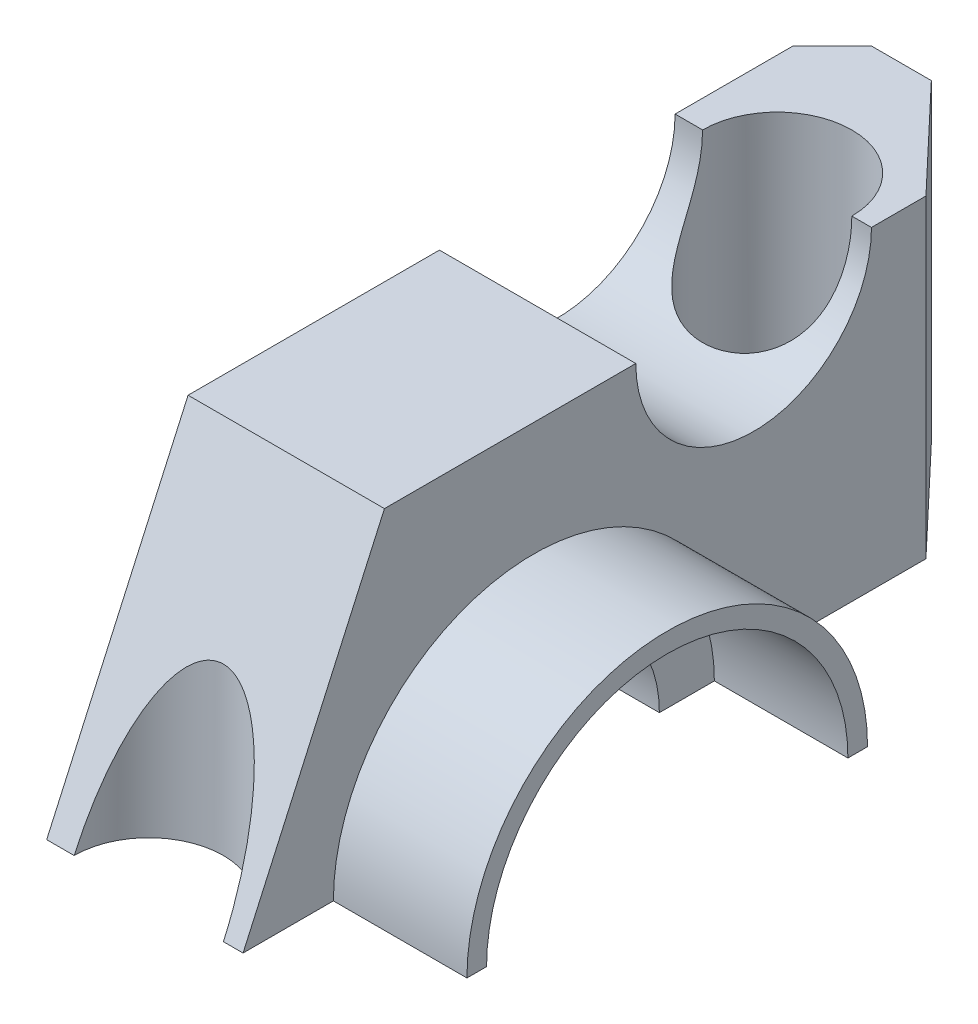
SolidWorks part; units mm, degrees
ref_plane "Alzado" through (0, 0, 0) normal (0, 0, 1) x (1, 0, 0)
ref_plane "Planta" through (0, 0, 0) normal (0, 1, 0) x (1, 0, 0)
ref_plane "Vista lateral" through (0, 0, 0) normal (1, 0, 0) x (0, 0, -1)
sketch "Croquis1" plane through (0, 0, 0) normal (1, 0, 0) x (0, 0, -1)
  line L0 (-100, 0) -> (-82, 40)
  line L1 (0, 0) -> (-100, 0)
  line L2 (0, 0) -> (0, 40)
  line L3 (0, 40) -> (-82, 40)
  dimension "D1" = 40
  dimension "D2" = 100
  dimension "D3" = 82
extrude "Saliente-Extruir1" add sketch "Croquis1" along normal blind 25
sketch "Croquis2" plane through (0, 40, 0) normal (0, 1, 0) x (1, 0, 0)
  line L1 (25, 0) -> (0, 0) construction
  line L2 (0, 0) -> (0, -82) construction
  circle A0 centre (13, -100) radius 9.5
  circle A1 centre (13, -20) radius 9.5
  point P8 (0, 0)
  dimension "D1" = 19
  dimension "D2" = 19
  dimension "D3" = 20
  dimension "D4" = 13
  dimension "D5" = 13
extrude "Cortar-Extruir1" cut sketch "Croquis2" against normal blind 94 and the other way blind 54
sketch "Croquis3" plane through (25, 0, 0) normal (1, 0, 0) x (0, 0, -1)
  line L0 (0, 40) -> (-82, 40) construction
  line L1 (0, 0) -> (0, 40) construction
  line L2 (-100, 0) -> (0, 0) construction
  circle A0 centre (-35, 40) radius 15
  circle A1 centre (-63, 0) radius 16
  dimension "D1" = 30
  dimension "D3" = 32
  dimension "D2" = 35
  dimension "D4" = 63
extrude "Cortar-Extruir2" cut sketch "Croquis3" against normal blind 94 and the other way blind 94
sketch "Croquis4" plane through (0, 40, 0) normal (0, 1, 0) x (1, 0, 0)
  line L0 (12.62, 0) -> (25, -13.0666)
  line L1 (25, 0) -> (0, 0) construction
  line L2 (25, 0) -> (25, -20) construction
  line L3 (0, 0) -> (0, -20) construction
  line L4 (12.62, 0) -> (25, 0)
  line L5 (25, 0) -> (25, -13.0666)
  dimension "D1" = 18
  dimension "D2" = 12.62
extrude "Cortar-Extruir3" cut sketch "Croquis4" against normal blind 94 and the other way blind 94
chamfer "Chaflán2" distance 5 angle 45 1 edges at (0, 20, 0)
sketch "Croquis5" plane through (25, 0, 0) normal (1, 0, 0) x (0, 0, -1)
  line L0 (-88.5, 0) -> (-86, 0)
  line L1 (-40, 0) -> (-37.5, 0)
  arc A0 (-40, 0) -> (-86, 0) centre (-63, 0) ccw
  arc A1 (-37.5, 0) -> (-88.5, 0) centre (-63, 0) ccw
  dimension "D1" = 46
  dimension "D2" = 51
extrude "Saliente-Extruir2" add sketch "Croquis5" along normal blind 17
